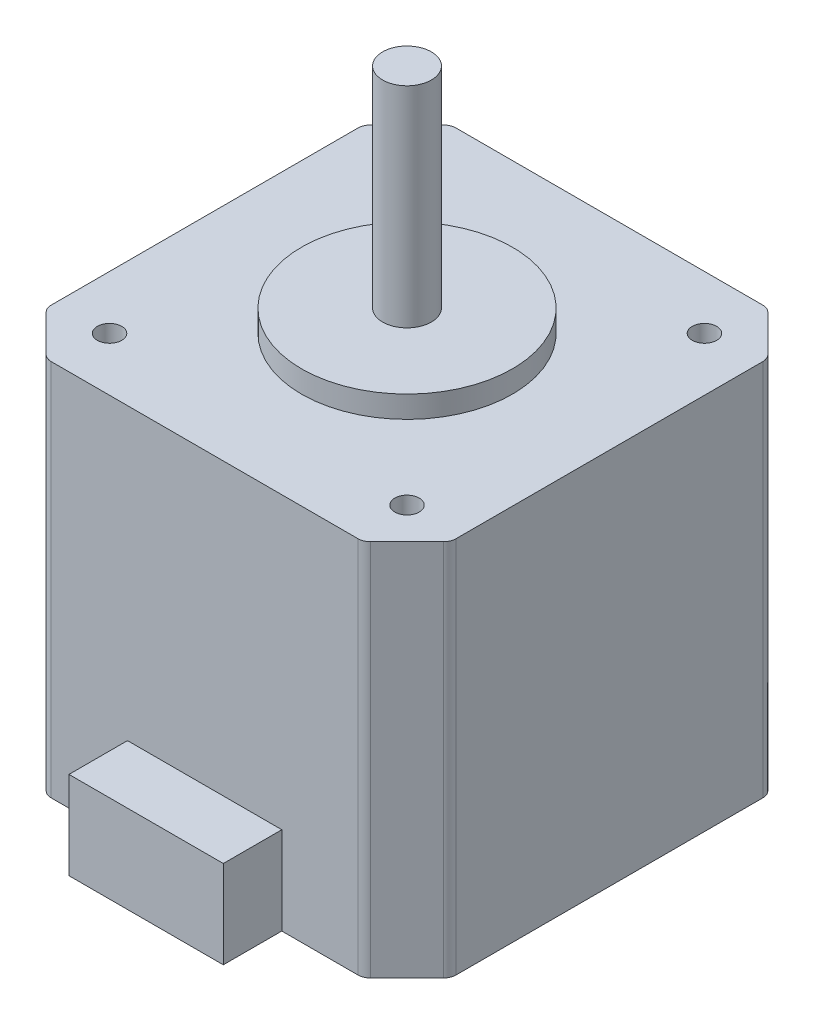
SolidWorks part; units mm, degrees
ref_plane "Front Plane" through (0, 0, 0) normal (0, 0, 1) x (1, 0, 0)
ref_plane "Top Plane" through (0, 0, 0) normal (0, 1, 0) x (1, 0, 0)
ref_plane "Right Plane" through (0, 0, 0) normal (1, 0, 0) x (0, 0, -1)
sketch "Sketch1" plane through (0, 0, 0) normal (0, 1, 0) x (1, 0, 0)
  line L0 (0, 0) -> (0, -24.13) construction
  line L1 (-21.082, -21.082) -> (21.082, -21.082)
  line L2 (-21.082, -21.082) -> (-21.082, 21.082)
  line L3 (-21.082, 21.082) -> (21.082, 21.082)
  line L4 (21.082, -21.082) -> (21.082, 21.082)
  line L5 (-21.082, -21.082) -> (21.082, 21.082) construction
  line L6 (-21.082, 21.082) -> (21.082, -21.082) construction
  line L7 (-8.0391, -21.082) -> (8.0391, -21.082)
  line L8 (-8.0391, -21.082) -> (-8.0391, -27.178)
  line L9 (-8.0391, -27.178) -> (8.0391, -27.178)
  line L10 (8.0391, -21.082) -> (8.0391, -27.178)
  line L11 (-8.0391, -21.082) -> (8.0391, -27.178) construction
  line L12 (-8.0391, -27.178) -> (8.0391, -21.082) construction
  point P0 (0, 0)
  point P10 (0, -24.13)
  dimension "D1" = 42.164
  dimension "D2" = 42.164
  dimension "D3" = 16.0782
  dimension "D4" = 6.096
extrude "Boss-Extrude1" add sketch "Sketch1" along normal blind 39.37 contours L1 L4 L3 L2 region at (0, 0, 0)
extrude "Boss-Extrude2" add sketch "Sketch1<3>" along normal blind 9.144 contours L10 L1 L8 L9 region at (0, 0, 24.13)
sketch "Sketch1<3>" plane through (0, 0, 0) normal (0, 1, 0) x (1, 0, 0) same geometry as "Sketch1"
sketch "Sketch2" plane through (0, 39.37, 0) normal (0, 1, 0) x (1, 0, 0)
  circle A0 centre (0, 0) radius 10.9855
  dimension "D1" = 21.971
extrude "Boss-Extrude3" add sketch "Sketch2" along normal blind 2.286
sketch "Sketch3" plane through (0, 41.656, 0) normal (0, 1, 0) x (1, 0, 0)
  circle A0 centre (0, 0) radius 2.54
  dimension "D1" = 5.08
extrude "Boss-Extrude4" add sketch "Sketch3" along normal blind 21.844
sketch "Sketch4" plane through (0, 39.37, 0) normal (0, 1, 0) x (1, 0, 0)
  line L0 (-21.082, -21.082) -> (-21.082, 21.082) construction
  line L1 (-15.494, -15.494) -> (15.494, -15.494) construction
  line L2 (-15.494, -15.494) -> (-15.494, 15.494) construction
  line L3 (-15.494, 15.494) -> (15.494, 15.494) construction
  line L4 (15.494, -15.494) -> (15.494, 15.494) construction
  line L5 (-15.494, -15.494) -> (15.494, 15.494) construction
  line L6 (-15.494, 15.494) -> (15.494, -15.494) construction
  line L7 (-21.082, 21.082) -> (21.082, 21.082) construction
  circle A0 centre (-15.494, 15.494) radius 1.27
  circle A1 centre (15.494, 15.494) radius 1.27
  circle A2 centre (15.494, -15.494) radius 1.27
  circle A3 centre (-15.494, -15.494) radius 1.27
  point P0 (0, 0)
  point P10 (-15.494, 16.764)
  point P11 (-16.764, 15.494)
  dimension "D1" = 2.54
  dimension "D2" = 4.318
  dimension "D3" = 4.318
extrude "Cut-Extrude1" cut sketch "Sketch4" against normal blind 6.35
sketch "Sketch5" plane through (0, 39.37, 0) normal (0, 1, 0) x (1, 0, 0)
  line L0 (-21.082, 16.51) -> (-16.51, 21.082)
  line L1 (-21.082, -21.082) -> (-21.082, 21.082) construction
  line L2 (-21.082, 21.082) -> (21.082, 21.082) construction
  line L3 (-16.51, 21.082) -> (16.51, 21.082) construction
  line L4 (16.51, 21.082) -> (21.082, 16.51)
  line L5 (21.082, -21.082) -> (21.082, 21.082) construction
  line L6 (21.082, 16.51) -> (21.082, -16.51) construction
  line L7 (21.082, -16.51) -> (16.51, -21.082)
  line L8 (-21.082, -21.082) -> (21.082, -21.082) construction
  line L9 (16.51, -21.082) -> (-16.51, -21.082) construction
  line L10 (-16.51, -21.082) -> (-21.082, -16.51)
  line L11 (-21.082, -16.51) -> (-21.082, 16.51) construction
  line L12 (-21.082, 16.51) -> (21.082, 16.51) construction
  line L13 (16.51, 21.082) -> (16.51, -21.082) construction
  line L14 (21.082, -16.51) -> (-21.082, -16.51) construction
  line L15 (-16.51, -21.082) -> (-16.51, 21.082) construction
  line L16 (-21.082, 16.51) -> (-21.082, 21.082)
  line L17 (-21.082, 21.082) -> (-16.51, 21.082)
  line L18 (16.51, 21.082) -> (21.082, 21.082)
  line L19 (21.082, 21.082) -> (21.082, 16.51)
  line L20 (-21.082, -16.51) -> (-21.082, -21.082)
  line L21 (-21.082, -21.082) -> (-16.51, -21.082)
  line L22 (16.51, -21.082) -> (21.082, -21.082)
  line L23 (21.082, -21.082) -> (21.082, -16.51)
  dimension "D1" = 4.572
extrude "Cut-Extrude2" cut sketch "Sketch5" against normal through all
fillet "Fillet1" radius 1.27 8 edges at (-21.082, 19.685, -16.51) (-16.51, 19.685, -21.082) (16.51, 19.685, -21.082) (21.082, 19.685, -16.51) (21.082, 19.685, 16.51) (16.51, 19.685, 21.082) (-21.082, 19.685, 16.51) (-16.51, 19.685, 21.082)
